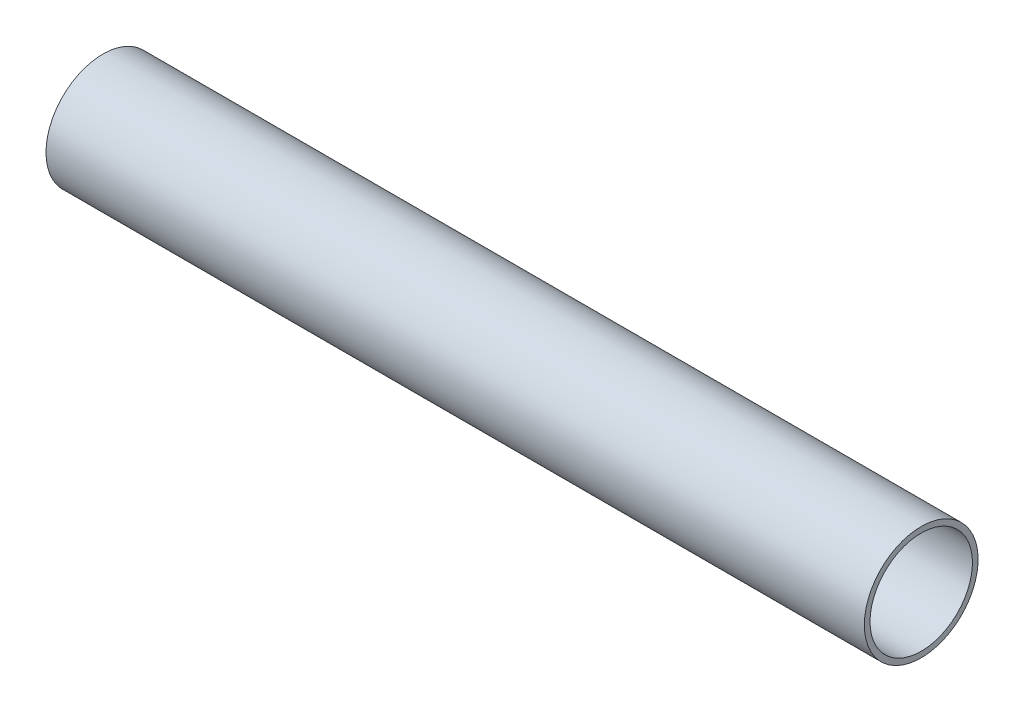
SolidWorks part; units mm, degrees
material "PC High Viscosity"
ref_plane "Front Plane" through (0, 0, 0) normal (0, 0, 1) x (1, 0, 0)
ref_plane "Top Plane" through (0, 0, 0) normal (0, 1, 0) x (1, 0, 0)
ref_plane "Right Plane" through (0, 0, 0) normal (1, 0, 0) x (0, 0, -1)
sketch "Sketch1" plane through (0, 0, 0) normal (1, 0, 0) x (0, 0, -1)
  circle A0 centre (0, 0) radius 15.875
  dimension "D1" = 31.75
extrude "Extrude-Thin1" add sketch "Sketch1" along normal mid plane 228.346 thin thin type one direction reverse wall 1.5875
